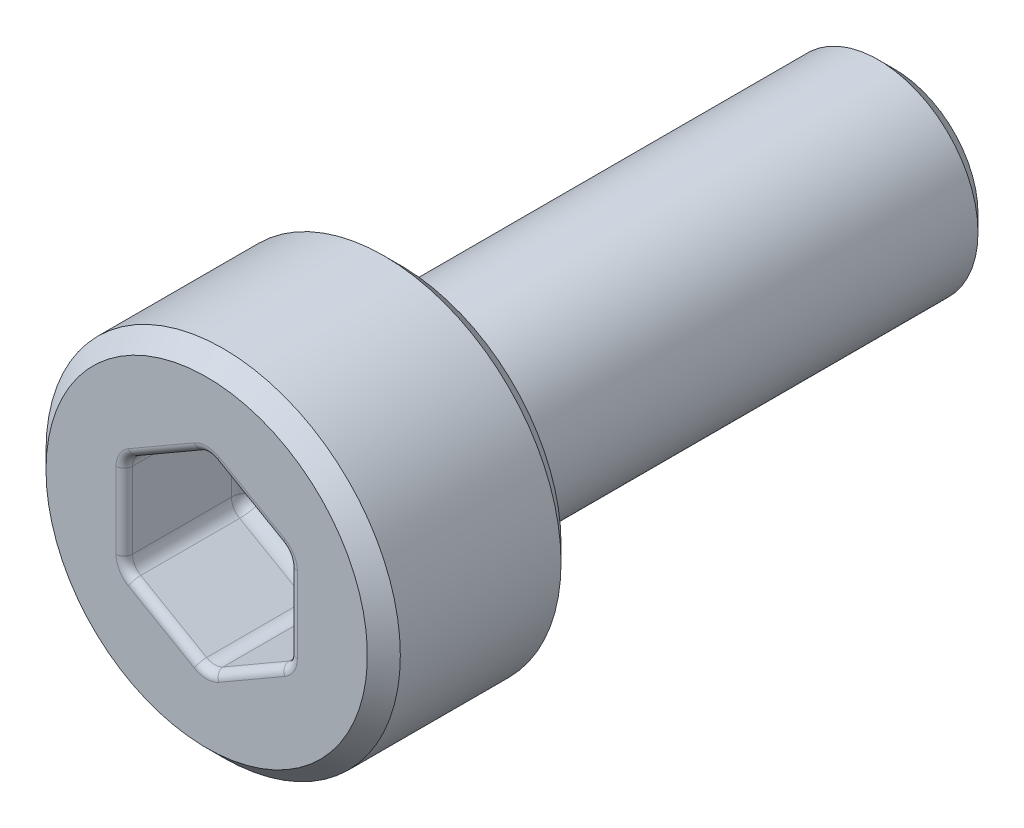
SolidWorks part; units mm, degrees
material "1.4000 (X6Cr13)"
ref_plane "Ebene vorne" through (0, 0, 0) normal (0, 0, 1) x (1, 0, 0)
ref_plane "Ebene oben" through (0, 0, 0) normal (0, 1, 0) x (1, 0, 0)
ref_plane "Ebene rechts" through (0, 0, 0) normal (1, 0, 0) x (0, 0, -1)
sketch "Skizze1" plane through (0, 0, 0) normal (1, 0, 0) x (0, 0, -1)
  line L0 (-21.9199, 0) -> (33.7608, 0) construction
  line L1 (0, 13.9907) -> (0, -9.4798) construction
  line L2 (-2.35, 0) -> (-2.35, 2.15)
  line L3 (-2.35, 2.15) -> (0, 2.15)
  line L4 (0, 2.15) -> (0, 1.21)
  line L5 (0, 1.21) -> (6, 1.21)
  line L6 (6, 1.21) -> (6, 0)
  line L7 (6, 0) -> (-2.35, 0)
  dimension "D1" = 2.42
  dimension "D2" = 2.35
  dimension "D3" = 4.3
  dimension "D4" = 6
revolve "Rotation1" add sketch "Skizze1" angle 360 about L0
sketch "Skizze2" plane through (0, 0, 2.35) normal (0, 0, 1) x (1, 0, 0)
  line L0 (0, 8.6995) -> (0, -7.3778) construction
  line L1 (1, -0.5774) -> (1, 0.5774)
  line L2 (1, 0.5774) -> (0, 1.1547)
  line L3 (0, 1.1547) -> (-1, 0.5774)
  line L4 (-1, 0.5774) -> (-1, -0.5774)
  line L5 (-1, -0.5774) -> (0, -1.1547)
  line L6 (0, -1.1547) -> (1, -0.5774)
  circle A0 centre (0, 0) radius 1 construction
  dimension "D1" = 2
extrude "Schnitt-Linear austragen1" cut sketch "Skizze2" against normal blind 1.5
chamfer "Fase1" distance 0.2 angle 45 3 edges at (2.15, 0, 2.35) (2.15, 0, 0) (1.21, 0, -6)
fillet "Verrundung1" radius 0.2 13 edges at (-0.5, -0.866, 0.85) (-1, 0, 0.85) (-0.5, 0.866, 0.85) (0.5, 0.866, 0.85) (1, 0, 0.85) (0.5, -0.866, 0.85) (-1, -0.5774, 1.6) (0, -1.1547, 1.6) (1, -0.5774, 1.6) (1, 0.5774, 1.6) (0, 1.1547, 1.6) (-1, 0.5774, 1.6) (1.21, 0, 0)
fillet "Verrundung2" radius 0.1 12 edges at (0.9732, -0.5619, 2.35) (0.5, -0.866, 2.35) (0, -1.1238, 2.35) (-0.5, -0.866, 2.35) (-0.9732, -0.5619, 2.35) (-1, 0, 2.35) (-0.9732, 0.5619, 2.35) (-0.5, 0.866, 2.35) (0, 1.1238, 2.35) (0.5, 0.866, 2.35) (0.9732, 0.5619, 2.35) (1, 0, 2.35)
ref_axis "Achse1" through (0, 0, -19.6323) along (0, 0, 1)
